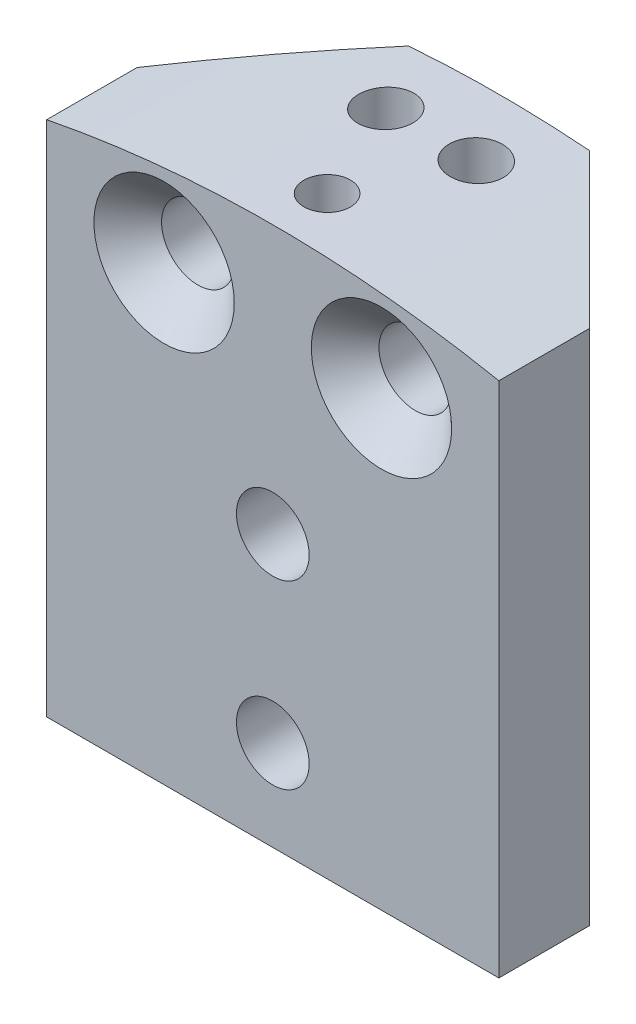
SolidWorks part; units mm, degrees
ref_plane "Front Plane" through (0, 0, 0) normal (0, 0, 1) x (1, 0, 0)
ref_plane "Top Plane" through (0, 0, 0) normal (0, 1, 0) x (1, 0, 0)
ref_plane "Right Plane" through (0, 0, 0) normal (1, 0, 0) x (0, 0, -1)
sketch "Sketch1" plane through (0, 0, 0) normal (0, 0, 1) x (1, 0, 0)
  line L0 (-25.4, 19.05) -> (25.4, -19.05) construction
  line L1 (-25.4, 19.05) -> (25.4, 19.05)
  line L2 (-25.4, 19.05) -> (-25.4, -19.05)
  line L3 (-25.4, -19.05) -> (25.4, -19.05)
  line L4 (25.4, 19.05) -> (25.4, -19.05)
  point P4 (0, 0)
  dimension "D1" = 50.8
  dimension "D2" = 38.1
extrude "Boss-Extrude1" add sketch "Sketch1" along normal blind 15.875
hole_wizard "1/4-20 Tapped Hole1" positions "Sketch2" profile "Sketch3" tap size "1/4-20" standard "ANSI Inch" end condition through all
sketch "Sketch2" plane through (0, 0, 15.875) normal (0, 0, 1) x (1, 0, 0)
  line L0 (0, 19.05) -> (0, 3.1224) construction
  line L1 (25.4, 19.05) -> (-25.4, 19.05) construction
  line L2 (-7.6327, 12.7) -> (7.6327, 12.7) construction
  point P0 (7.6327, 12.7)
  point P2 (-7.6327, 12.7)
  point P17 (0, 12.7)
  dimension "D1" = 15.2654
  dimension "D2" = 6.35
cosmetic thread "Hole Thread1" parameters "D2"=6.35
cosmetic thread "Hole Thread2" parameters "D2"=6.35
sketch "Sketch3" plane through (7.6327, 12.7, 15.875) normal (1, 0, 0) x (0, -1, 0)
  line L0 (0, 0) -> (0, 15.875)
  line L1 (0, 15.875) -> (2.5527, 15.875)
  line L2 (2.5527, 15.875) -> (2.5527, 0)
  line L5 (2.5527, 0) -> (0, 0)
  line L11 (0, -6.35) -> (0, 107.95) construction
  dimension "Thru Tap Drill Dia." = 5.1054
  dimension "Thru Tap Drill Depth" = 15.875
sketch "Sketch4" plane through (0, 0, 15.875) normal (0, 0, 1) x (1, 0, 0)
  line L0 (-7.6327, 12.7) -> (0, -63.1168) construction
  line L1 (0, -63.1168) -> (7.6327, 12.7) construction
  line L2 (-39.2823, 8.7938) -> (-52.7044, 33.3644)
  line L3 (-52.7044, 33.3644) -> (0, 61.9277)
  line L4 (0, 61.9277) -> (62.6678, 36.7718)
  line L5 (62.6678, 36.7718) -> (48.5919, 2.8609)
  arc A0 (-39.2823, 8.7938) -> (48.5919, 2.8609) centre (0, -63.1168) cw
  circle A1 centre (7.6327, 12.7) radius 2.5527 construction
  circle A2 centre (-7.6327, 12.7) radius 2.5527 construction
  circle A3 centre (7.6327, 12.7) radius 2.5527 construction
  circle A4 centre (-7.6327, 12.7) radius 2.5527 construction
  dimension "D1" = 81.9404
  dimension "D2" = 76.2
extrude "Cut-Extrude1" cut sketch "Sketch4" against normal through all both and the other way through all
sketch "Sketch5" plane through (0, 0, 0) normal (0, 0, 1) x (1, 0, 0)
  line L0 (0, 40.1112) -> (0, -19.05) construction
  line L1 (-25.4, -19.05) -> (25.4, -19.05) construction
  line L2 (-6.35, 65.2565) -> (-6.35, -49.5068)
  line L3 (79.6342, 65.2565) -> (6.35, 65.2565)
  line L4 (79.6342, 65.2565) -> (79.6342, -49.5068)
  line L5 (79.6342, -49.5068) -> (6.35, -49.5068)
  line L6 (6.35, 65.2565) -> (6.35, -49.5068)
  line L7 (-79.6342, -49.5068) -> (-6.35, -49.5068)
  line L8 (-79.6342, 65.2565) -> (-79.6342, -49.5068)
  line L9 (-79.6342, 65.2565) -> (-6.35, 65.2565)
  dimension "D1" = 6.35
extrude "Cut-Extrude3" cut sketch "Sketch5" along normal through all draft 45
sketch "Sketch6" plane through (0, 0, 15.875) normal (0, 0, 1) x (1, 0, 0)
  circle A0 centre (-7.6327, 12.7) radius 4.9276
  circle A1 centre (7.6327, 12.7) radius 4.9276
  dimension "D1" = 9.8552
extrude "Cut-Extrude4" cut sketch "Sketch6" against normal blind 12.7 draft 45
sketch "Sketch7" plane through (0, 0, 15.875) normal (0, 0, 1) x (1, 0, 0)
  line L0 (-15.875, 35.1886) -> (15.875, -35.1886) construction
  line L1 (-15.875, 35.1886) -> (15.875, 35.1886)
  line L2 (-15.875, 35.1886) -> (-15.875, -35.1886)
  line L3 (-15.875, -35.1886) -> (15.875, -35.1886)
  line L4 (15.875, 35.1886) -> (15.875, -35.1886)
  line L5 (22.225, -19.05) -> (22.225, 15.752) construction
  line L7 (-74.0636, 49.8416) -> (64.4715, 49.8416)
  line L8 (-74.0636, 49.8416) -> (-74.0636, -74.2127)
  line L9 (-74.0636, -74.2127) -> (64.4715, -74.2127)
  line L10 (64.4715, 49.8416) -> (64.4715, -74.2127)
  point P4 (0, 0)
  dimension "D1" = 6.35
extrude "Cut-Extrude5" cut sketch "Sketch7" against normal through all both and the other way through all
hole_wizard "1/4-20 Tapped Hole2" positions "Sketch8" profile "Sketch9" tap size "1/4-20" standard "ANSI Inch" end condition through all
sketch "Sketch8" plane through (0, 0, 15.875) normal (0, 0, 1) x (1, 0, 0)
  line L0 (0, -19.05) -> (0, -12.7) construction
  line L1 (-15.875, -19.05) -> (15.875, -19.05) construction
  point P0 (0, -12.7)
  point P11 (0, 0)
  point P14 (0, 0)
  point P15 (0, -18.0211)
  dimension "D1" = 12.7
  dimension "D2" = 6.35
sketch "Sketch9" plane through (0, -12.7, 15.875) normal (1, 0, 0) x (0, -1, 0)
  line L0 (0, 0) -> (0, 15.875)
  line L1 (0, 15.875) -> (2.5527, 15.875)
  line L2 (2.5527, 15.875) -> (2.5527, 0)
  line L5 (2.5527, 0) -> (0, 0)
  line L11 (0, -6.35) -> (0, 107.95) construction
  dimension "Thru Tap Drill Dia." = 5.1054
  dimension "Thru Tap Drill Depth" = 15.875
cosmetic thread "Hole Thread3" parameters "D2"=6.35
cosmetic thread "Hole Thread4" parameters "D2"=6.35
ref_plane "Plane1" through (0, 19.05, 0) normal (0, -1, 0) x (-1, 0, 0)
hole_wizard "#10-24 Tapped Hole2" positions "Sketch11" profile "Sketch12" tap size "#10-24" standard "ANSI Inch"
sketch "Sketch11" plane through (0, 19.05, 0) normal (0, -1, 0) x (-1, 0, 0)
  circle A0 centre (3.175, -4.7625) radius 1.8986 construction
  circle A1 centre (-3.175, -4.7625) radius 1.8986 construction
  circle A2 centre (3.175, -4.7625) radius 1.8987 construction
  circle A3 centre (-3.175, -4.7625) radius 1.8987 construction
  point P0 (3.175, -4.7625)
  point P2 (-3.175, -4.7625)
  point P10 (0, 0)
  point P11 (0, 0)
sketch "Sketch12" plane through (-3.175, 19.05, 4.7625) normal (1, 0, 0) x (0, 0, 1)
  line L0 (0, 0) -> (0, 13.8408)
  line L1 (0, 13.8408) -> (1.8986, 12.7)
  line L2 (1.8986, 12.7) -> (1.8986, 0)
  line L5 (1.8986, 0) -> (0, 0)
  line L10 (0, 13.8408) -> (-1.8987, 12.7) construction
  line L11 (0, -6.35) -> (0, 107.95) construction
  dimension "Tap Drill Dia." = 3.7973
  dimension "Tap Drill Depth" = 12.7
  dimension "Drill Angle" = 118
cosmetic thread "Hole Thread9" parameters "D1"=12.7, "D2"=4.826
cosmetic thread "Hole Thread10" parameters "D1"=12.7, "D2"=4.826
sketch "Sketch13" plane through (0, 19.05, 0) normal (0, -1, 0) x (-1, 0, 0)
  spline S0 degree 3 poles (1.6302, -12.065) (1.6302, -8.8011) (-1.6337, -8.8011) (-1.6337, -12.065) (-1.6337, -15.3289) (1.6302, -15.3289) (1.6302, -12.065) (1.6302, -8.8011) (-1.6337, -8.8011) knots -0.5 0 0 0 0.5 0.5 0.5 1 1 1 1.5 1.5 1.5 weights 1 0.333333 0.333333 1 0.333333 0.333333 1 0.333333 0.333333 only from (1.6302, -12.065) to (1.6302, -12.065) construction
  spline S1 degree 3 poles (1.6302, -12.065) (1.6302, -8.8011) (-1.6337, -8.8011) (-1.6337, -12.065) (-1.6337, -15.3289) (1.6302, -15.3289) (1.6302, -12.065) (1.6302, -8.8011) (-1.6337, -8.8011) knots -0.5 0 0 0 0.5 0.5 0.5 1 1 1 1.5 1.5 1.5 weights 1 0.333333 0.333333 1 0.333333 0.333333 1 0.333333 0.333333 only from (1.6302, -12.065) to (1.6302, -12.065)
extrude "Cut-Extrude6" cut sketch "Sketch13" along normal blind 6.35
